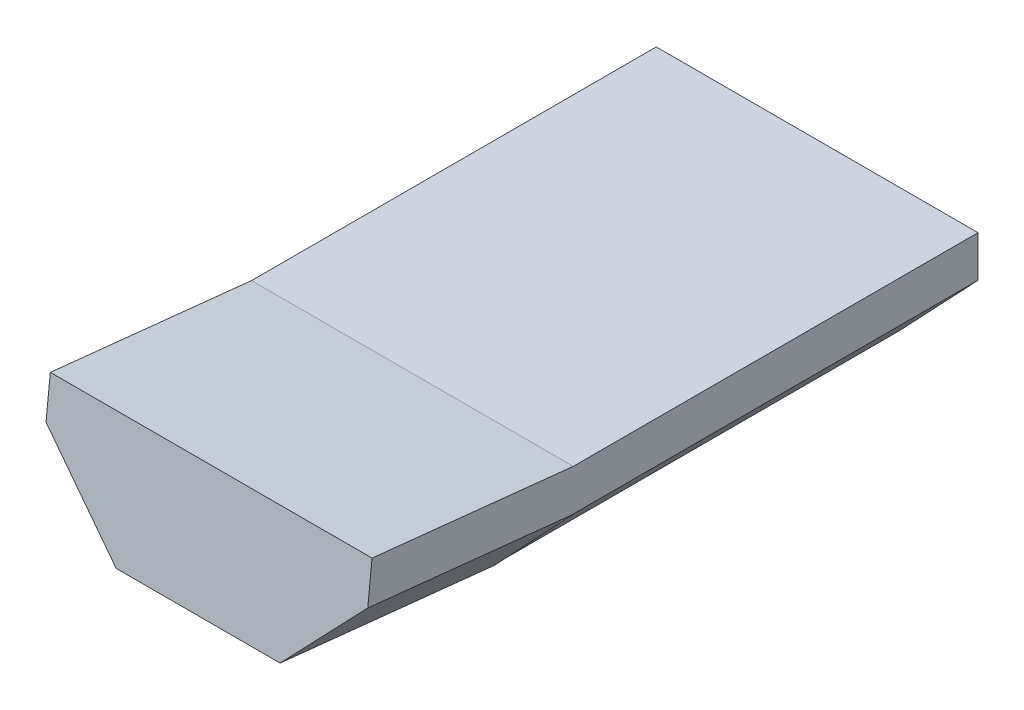
SolidWorks part; units mm, degrees
ref_plane "Front Plane" through (0, 0, 0) normal (0, 0, 1) x (1, 0, 0)
ref_plane "Top Plane" through (0, 0, 0) normal (0, 1, 0) x (1, 0, 0)
ref_plane "Right Plane" through (0, 0, 0) normal (1, 0, 0) x (0, 0, -1)
sketch "Sketch3" plane through (0, 0, 0) normal (0, 0, 1) x (1, 0, 0)
  line L0 (-7.95, 0) -> (7.95, 0)
  line L1 (7.95, 0) -> (7.95, -2.04)
  line L2 (7.95, -2.04) -> (4.05, -6.1557)
  line L3 (-7.95, -2.04) -> (-4.05, -6.1557)
  line L4 (0, 0) -> (0, 4.8752) construction
  line L5 (-7.95, 0) -> (-7.95, -2.04)
  line L6 (-4.05, -6.1557) -> (4.05, -6.1557)
  dimension "D1" = 2.04
  dimension "D2" = 5.67
  dimension "D3" = 15.9
  dimension "D4" = 8.1
extrude "Boss-Extrude1" add sketch "Sketch3" along normal blind 20
ref_plane "Plane1" through (0, 0, 0) normal (1, 0, 0) x (0, 0, -1)
sketch "Sketch4" plane through (0, 0, 0) normal (1, 0, 0) x (0, 0, -1)
  line L0 (-20, 0) -> (-29.9452, 1.0453)
  line L1 (-29.9452, 1.0453) -> (-30.1543, -0.9438)
  line L2 (-30.1543, -0.9438) -> (-20, -2.011)
  line L3 (-20, -6.1557) -> (-20, -2.04) construction
  line L4 (-20, -2.04) -> (-20, 0) construction
  line L5 (-20, 0) -> (0, 0) construction
  line L6 (-20, 0) -> (-20, -2.011)
  dimension "D1" = 174
  dimension "D2" = 2
  dimension "D3" = 10
extrude "Boss-Extrude2" add sketch "Sketch4" along normal mid plane 4
sketch "Sketch5" plane through (0, 3.1244, 29.7267) normal (0, 0.1045, 0.9945) x (1, 0, 0)
  line L0 (-7.95, -4.1306) -> (-4.05, -8.2463)
  line L1 (2, -2.0906) -> (-2, -2.0906) construction
  line L2 (7.95, -2.0906) -> (7.95, -4.1306)
  line L3 (7.95, -4.1306) -> (4.05, -8.2463)
  line L4 (4.05, -8.2463) -> (-4.05, -8.2463)
  line L5 (0, -1.122) -> (0, 1.122) construction
  line L6 (0, -2.0906) -> (0, 6.5913) construction
  line L7 (-7.95, -2.0906) -> (-7.95, -4.1306)
  line L8 (-7.95, -2.0906) -> (7.95, -2.0906)
  point P14 (0, -8.2463)
  dimension "D1" = 2.04
  dimension "D2" = 5.67
  dimension "D3" = 8.1
extrude "Boss-Extrude3" add sketch "Sketch5" against normal up to surface (10 mm away) up to face at (0, -2.0413, 20)
